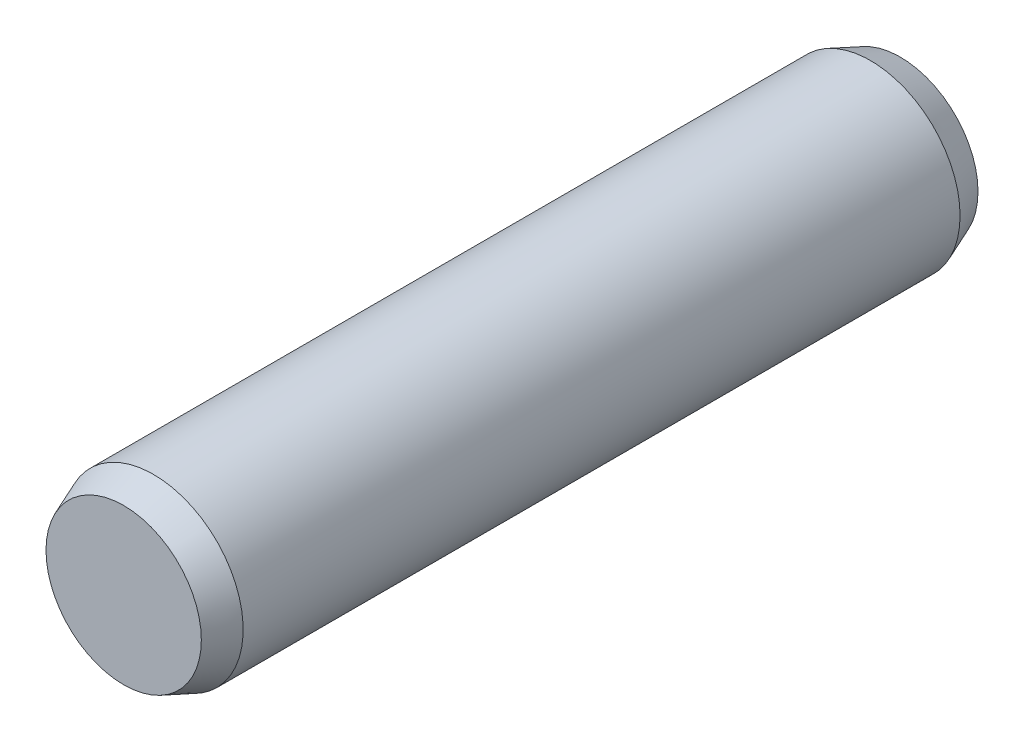
SolidWorks part; units mm, degrees
ref_plane "Front Plane" through (0, 0, 0) normal (0, 0, 1) x (1, 0, 0)
ref_plane "Top Plane" through (0, 0, 0) normal (0, 1, 0) x (1, 0, 0)
ref_plane "Right Plane" through (0, 0, 0) normal (1, 0, 0) x (0, 0, -1)
sketch "Sketch1" plane through (0, 0, 0) normal (0, 0, 1) x (1, 0, 0)
  circle A0 centre (0, 0) radius 1.5
  dimension "D1" = 3
extrude "Boss-Extrude1" add sketch "Sketch1" along normal mid plane 13
chamfer "Chamfer1" distance 0.5 distance2 0.2 1 edges at (1.5, 0, 6.5) first distance on face at (1.5, 0, 6.5)
chamfer "Chamfer2" distance 0.2 distance2 0.5 1 edges at (1.5, 0, -6.5) first distance on face at (1.5, 0, -6.5)
